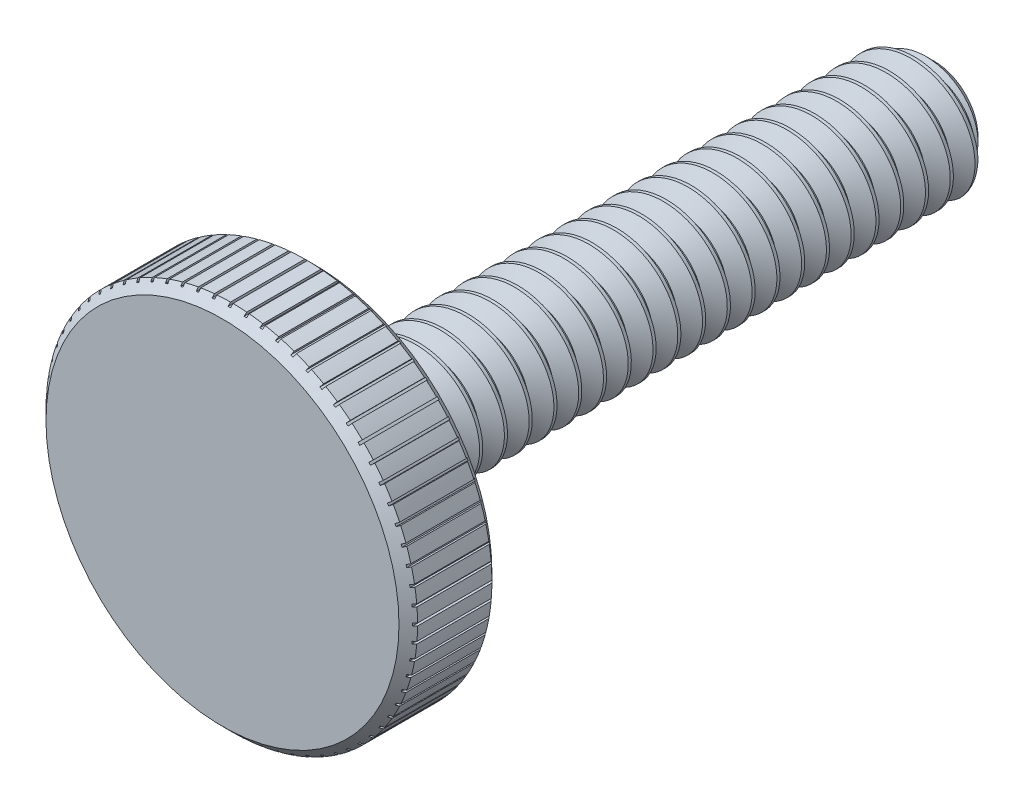
SolidWorks part; units mm, degrees
ref_plane "Front" through (0, 0, 0) normal (0, 0, 1) x (1, 0, 0)
ref_plane "Top" through (0, 0, 0) normal (0, 1, 0) x (1, 0, 0)
ref_plane "Right" through (0, 0, 0) normal (1, 0, 0) x (0, 0, -1)
sketch "Sketch20" plane through (0, 0, 0) normal (1, 0, 0) x (0, 0, -1)
  line L0 (0, 0) -> (31.75, 0) construction
  line L1 (31.75, 3.175) -> (31.75, -3.175) construction
  line L2 (0, 9.525) -> (0, -9.525) construction
  line L3 (-4.7625, 9.525) -> (-4.7625, -9.525) construction
  line L4 (0, 3.7703) -> (0, -3.7703) construction
  point P9 (26.035, -3.175)
  point P11 (0, 0)
  point P14 (0, 0)
  dimension "D1" = 6.35
  dimension "D2" = 31.75
  dimension "D3" = 5.715
  dimension "Head Diameter" = 19.05
  dimension "Head Height" = 4.7625
sketch "Sketch1" plane through (0, 0, 0) normal (0, 0, 1) x (1, 0, 0)
  circle A0 centre (0, 0) radius 3.175
  dimension "dia" = 6.35
extrude "Extrude1" add sketch "Sketch1" against normal blind 31.75
chamfer "Chamfer2" distance 0.9525 angle 45 1 edges at (3.175, 0, -31.75)
sketch "Sketch15" plane through (0, 0, -31.75) normal (0, 0, -1) x (-1, 0, 0)
  circle A0 centre (0, 0) radius 3.175 construction
  circle A2 centre (0, 0) radius 3.175
curve "Helix/Spiral1" pitch 1.27 height 33.02 turns 26 parameters "pitch"=1.27
sketch "Sketch14" plane through (0, 0, 0) normal (1, 0, 0) x (0, 0, -1)
  line L0 (31.75, 3.175) -> (32.8612, 3.175)
  line L1 (32.8612, 3.175) -> (32.385, 2.3501)
  line L2 (32.385, 2.3501) -> (32.2263, 2.3501)
  line L3 (32.2263, 2.3501) -> (31.75, 3.175)
  line L4 (31.9881, 2.7626) -> (32.6231, 2.7626) construction
  line L5 (31.75, -3.175) -> (31.75, 3.175) construction
  dimension "D1" = 0.1588
  dimension "D2" = 0.635
  dimension "D3" = 60
sweep "Cut-Sweep1" cut profiles "Sketch14" path "Helix/Spiral1" align with end faces yes
sketch "Sketch21" plane through (0, 0, 0) normal (0, 0, 1) x (1, 0, 0)
  line L0 (-9.525, 0) -> (9.525, 0) construction
  circle A0 centre (0, 0) radius 9.525
extrude "Boss-Extrude1" add sketch "Sketch21" along normal up to vertex (4.7625 mm away) up to point (0, -9.525, 4.7625)
chamfer "Chamfer3" distance 0.4763 angle 45 2 edges at (9.525, 0, 0) (9.525, 0, 4.7625)
ref_plane "Plane1" through (0, 9.525, 0) normal (0, 1, 0) x (-1, 0, 0)
sketch "Sketch22" plane through (0, 9.525, 0) normal (0, 1, 0) x (-1, 0, 0)
  line L0 (0, 4.7625) -> (0, 0) construction
  line L1 (-0.0635, 4.7625) -> (0.0635, 4.7625)
  line L3 (-0.0635, 4.7625) -> (-0.0635, 0)
  line L4 (-0.0635, 0) -> (0.0635, 0)
  line L7 (0.0635, 4.7625) -> (0.0635, 0)
  dimension "D1" = 0.127
extrude "Cut-Extrude1" cut sketch "Sketch22" against normal offset from surface (0.1272 mm away) 0.127
pattern_circular "CirPattern1" count 72 over 360 about axis through (0, 0, 0) along (0, 0, 1) of "Cut-Extrude1"
equation "\"D3@Helix/Spiral1\" = \"Lg@Extrude1\"+\"pitch@Helix/Spiral1\""
equation "\"D1@Sketch14\" = \"pitch@Helix/Spiral1\" * .125"
equation "\"D2@Sketch14\" = \"pitch@Helix/Spiral1\" * .5"
equation "\"D1@Chamfer2\" = \"pitch@Helix/Spiral1\" * .75"
equation "\"D1@Sketch20\" = \"dia@Sketch1\""
equation "\"D2@Sketch20\" = \"Lg@Extrude1\""
equation "\"D1@Chamfer3\" =\"Head Height@Sketch20\"/10"
equation "\"D3@Sketch20\" = \"pitch@Helix/Spiral1\"*4.50"
